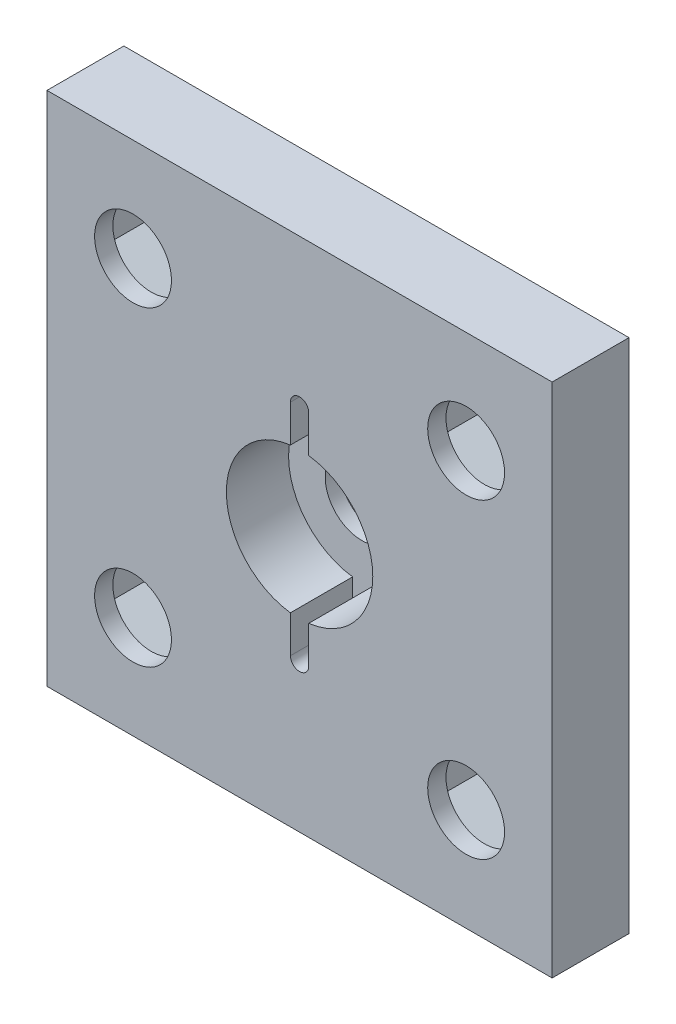
SolidWorks part; units mm, degrees
ref_plane "Front Plane" through (0, 0, 0) normal (0, 0, 1) x (1, 0, 0)
ref_plane "Top Plane" through (0, 0, 0) normal (0, 1, 0) x (1, 0, 0)
ref_plane "Right Plane" through (0, 0, 0) normal (1, 0, 0) x (0, 0, -1)
sketch "Sketch1" plane through (0, 0, 0) normal (0, 0, 1) x (1, 0, 0)
  line L0 (-8.89, 10.795) -> (8.89, 10.795) construction
  line L1 (17.526, 17.907) -> (-17.526, 17.907)
  line L2 (17.526, 17.907) -> (17.526, -17.907)
  line L3 (17.526, -17.907) -> (-17.526, -17.907)
  line L4 (-17.526, 17.907) -> (-17.526, -17.907)
  line L5 (17.526, 17.907) -> (-17.526, -17.907) construction
  line L6 (17.526, -17.907) -> (-17.526, 17.907) construction
  line L7 (0, 10.795) -> (0, -10.795) construction
  line L8 (-8.89, -10.795) -> (8.89, -10.795) construction
  circle A0 centre (-11.557, 10.795) radius 2.667
  circle A1 centre (11.557, 10.795) radius 2.667
  circle A2 centre (11.557, -10.795) radius 2.667
  circle A3 centre (-11.557, -10.795) radius 2.667
  point P0 (0, 0)
  point P22 (0, 0)
  dimension "D3" = 5.334
  dimension "D4" = 16.256
  dimension "D5" = 17.78
  dimension "D1" = 35.052
  dimension "D2" = 35.814
extrude "Boss-Extrude1" add sketch "Sketch1" along normal blind 5.334
sketch "Sketch2" plane through (0, 0, 0) normal (0, 0, -1) x (-1, 0, 0)
  line L1 (-11.557, 5.9557) -> (-7.366, 8.3753)
  line L2 (-7.366, 8.3753) -> (-7.366, 13.2147)
  line L3 (-7.366, 13.2147) -> (-11.557, 15.6343)
  line L4 (-11.557, 15.6343) -> (-15.748, 13.2147)
  line L5 (-15.748, 13.2147) -> (-15.748, 8.3753)
  line L6 (-15.748, 8.3753) -> (-11.557, 5.9557)
  line L7 (-11.557, -15.6343) -> (-7.366, -13.2147)
  line L8 (-7.366, -13.2147) -> (-7.366, -8.3753)
  line L9 (-7.366, -8.3753) -> (-11.557, -5.9557)
  line L10 (-11.557, -5.9557) -> (-15.748, -8.3753)
  line L11 (-15.748, -8.3753) -> (-15.748, -13.2147)
  line L12 (-15.748, -13.2147) -> (-11.557, -15.6343)
  line L13 (11.557, -15.6343) -> (15.748, -13.2147)
  line L14 (15.748, -13.2147) -> (15.748, -8.3753)
  line L15 (15.748, -8.3753) -> (11.557, -5.9557)
  line L16 (11.557, -5.9557) -> (7.366, -8.3753)
  line L17 (7.366, -8.3753) -> (7.366, -13.2147)
  line L18 (7.366, -13.2147) -> (11.557, -15.6343)
  line L19 (11.557, 5.9557) -> (15.748, 8.3753)
  line L20 (15.748, 8.3753) -> (15.748, 13.2147)
  line L21 (15.748, 13.2147) -> (11.557, 15.6343)
  line L22 (11.557, 15.6343) -> (7.366, 13.2147)
  line L23 (7.366, 13.2147) -> (7.366, 8.3753)
  line L24 (7.366, 8.3753) -> (11.557, 5.9557)
  circle A0 centre (-11.557, 10.795) radius 4.191 construction
  circle A1 centre (-11.557, -10.795) radius 4.191 construction
  circle A2 centre (11.557, -10.795) radius 4.191 construction
  circle A3 centre (11.557, 10.795) radius 4.191 construction
  point P28 (-7.366, 10.795)
  dimension "D1" = 8.382
extrude "Cut-Extrude1" cut sketch "Sketch2" against normal offset from surface (4.064 mm away) 1.27 up to face at (0, 0, 5.334)
sketch "Sketch3" plane through (0, 0, 5.334) normal (0, 0, 1) x (1, 0, 0)
  circle A0 centre (0, 0) radius 5.08
  dimension "D1" = 10.16
extrude "Cut-Extrude2" cut sketch "Sketch3" against normal blind 4.318
sketch "Sketch4" plane through (0, 0, 5.334) normal (0, 0, 1) x (1, 0, 0)
  line L0 (0, -7.62) -> (0, 7.62) construction
  line L1 (-0.635, -7.62) -> (-0.635, 7.62)
  line L2 (0.635, -7.62) -> (0.635, 7.62)
  arc A0 (-0.635, -7.62) -> (0.635, -7.62) centre (0, -7.62) ccw
  arc A1 (0.635, 7.62) -> (-0.635, 7.62) centre (0, 7.62) ccw
  point P2 (0, 0)
  dimension "D1" = 1.27
  dimension "D2" = 15.24
extrude "Cut-Extrude3" cut sketch "Sketch4" against normal blind 4.318
sketch "Sketch5" plane through (0, 0, 1.016) normal (0, 0, 1) x (1, 0, 0)
  circle A0 centre (0, 0) radius 2.54
  dimension "D1" = 5.08
extrude "Cut-Extrude4" cut sketch "Sketch5" against normal through all
